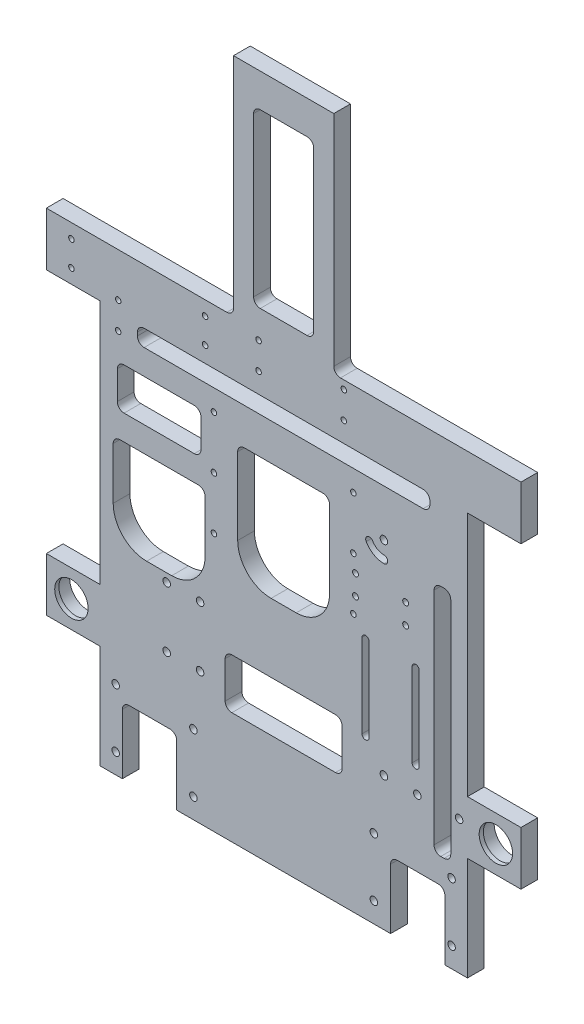
SolidWorks part; units mm, degrees
ref_plane "Front" through (0, 0, 0) normal (0, 0, 1) x (1, 0, 0)
ref_plane "Top" through (0, 0, 0) normal (0, 1, 0) x (1, 0, 0)
ref_plane "Right" through (0, 0, 0) normal (1, 0, 0) x (0, 0, -1)
sketch "Esquisse1" plane through (0, 0, 0) normal (0, 0, 1) x (1, 0, 0)
  line L1 (0, 0) -> (220, 0)
  line L2 (0, 0) -> (0, 285)
  line L3 (0, 285) -> (220, 285)
  line L4 (220, 0) -> (220, 285)
  dimension "D1" = 220
  dimension "D2" = 285
extrude "Boss.-Extru.1" add sketch "Esquisse1" along normal blind 10
sketch "Esquisse2" plane through (0, 0, 0) normal (0, -1, 0) x (1, 0, 0)
  line L0 (0, 5) -> (220, 5) construction
  line L1 (0, 10) -> (0, 0) construction
  line L2 (220, 10) -> (220, 0) construction
  line L3 (110, 5) -> (110, 28.0559) construction
  circle A0 centre (110, 5) radius 2
  circle A1 centre (213, 5) radius 2
  circle A2 centre (7, 5) radius 2
  dimension "D1" = 4
  dimension "D2" = 103
extrude "Enlèv. mat.-Extru.1" cut sketch "Esquisse2" against normal blind 8
sketch "Esquisse3" plane through (0, 0, 10) normal (0, 0, 1) x (1, 0, 0)
  line L0 (110, 0) -> (110, 285) construction
  line L1 (0, 0) -> (220, 0) construction
  line L2 (220, 285) -> (0, 285) construction
  line L3 (82.5, 208) -> (137.5, 208)
  line L4 (137.5, 208) -> (137.5, 138)
  line L5 (137.5, 138) -> (82.5, 138)
  line L6 (82.5, 208) -> (82.5, 138)
  line L8 (8, 175) -> (63, 175)
  line L9 (8, 175) -> (8, 120)
  line L10 (8, 120) -> (63, 120)
  line L11 (63, 175) -> (63, 120)
  line L12 (200, 55) -> (210, 55)
  line L13 (200, 55) -> (200, 195)
  line L14 (200, 195) -> (210, 195)
  line L15 (210, 55) -> (210, 195)
  point P11 (110, 138)
  point P12 (110, 208)
  dimension "D1" = 70
  dimension "D2" = 55
  dimension "D3" = 138
  dimension "D4" = 55
  dimension "D5" = 47
  dimension "D6" = 55
  dimension "D7" = 120
  dimension "D8" = 140
  dimension "D9" = 55
  dimension "D10" = 90
  dimension "D11" = 10
extrude "Enlèv. mat.-Extru.2" cut sketch "Esquisse3" against normal through all both and the other way through all
sketch "Esquisse5" plane through (0, 0, 10) normal (0, 0, 1) x (1, 0, 0)
  line L0 (110, 230) -> (110, 0) construction
  line L1 (22.5, 240) -> (197.5, 240)
  line L2 (22.5, 240) -> (22.5, 230)
  line L3 (22.5, 230) -> (197.5, 230)
  line L4 (197.5, 240) -> (197.5, 230)
  line L5 (0, 0) -> (220, 0) construction
  dimension "D1" = 175
  dimension "D2" = 10
  dimension "D3" = 230
extrude "Enlèv. mat.-Extru.3" cut sketch "Esquisse5" against normal through all both and the other way through all
sketch "Esquisse6" plane through (0, 0, 10) normal (0, 0, 1) x (1, 0, 0)
  line L0 (170, 80) -> (190, 80) construction
  line L1 (0, 0) -> (220, 0) construction
  line L2 (137.5, 138) -> (82.5, 138) construction
  line L3 (215, 80) -> (190, 80) construction
  line L4 (168, 193.9299) -> (168, 170.25) construction
  line L5 (186.4274, 170.25) -> (149.5726, 170.25) construction
  line L6 (0, 285) -> (0, 0) construction
  circle A0 centre (190, 80) radius 2.25
  circle A1 centre (170, 80) radius 2.25
  circle A2 centre (215, 80) radius 2.25
  circle A3 centre (153, 176.25) radius 1.75
  circle A4 centre (183, 176.25) radius 1.75
  circle A5 centre (183, 164.25) radius 1.75
  circle A6 centre (153, 164.25) radius 1.75
  point P8 (110, 138)
  dimension "D1" = 4.5
  dimension "D3" = 80
  dimension "D6" = 30
  dimension "D7" = 12
  dimension "D8" = 3.5
  dimension "D2" = 20
  dimension "D4" = 60
  dimension "D5" = 25
  dimension "D9" = 168
  dimension "D10" = 170.25
extrude "Enlèv. mat.-Extru.4" cut sketch "Esquisse6" against normal through all both and the other way through all
sketch "Esquisse7" plane through (0, 0, 10) normal (0, 0, 1) x (1, 0, 0)
  line L0 (110, 0) -> (110, 285) construction
  line L1 (0, 0) -> (220, 0) construction
  line L2 (220, 285) -> (0, 285) construction
  line L3 (68.285, 186) -> (68.285, 217.4) construction
  line L4 (68.285, 186) -> (110, 186) construction
  line L5 (151.715, 186) -> (151.715, 217.4) construction
  line L6 (95, 268) -> (120.5, 268) construction
  line L7 (120.5, 268) -> (120.5, 260) construction
  line L8 (120.5, 260) -> (137.9818, 260) construction
  line L9 (95, 252) -> (120.5, 252) construction
  line L10 (22.5, 240) -> (197.5, 240) construction
  circle A0 centre (68.285, 217.4) radius 1.65
  circle A1 centre (68.285, 186) radius 1.65
  circle A2 centre (68.285, 154.6) radius 1.65
  circle A3 centre (151.715, 154.6) radius 1.65
  circle A4 centre (151.715, 186) radius 1.65
  circle A5 centre (151.715, 217.4) radius 1.65
  circle A6 centre (95, 268) radius 1.65
  circle A7 centre (146, 268) radius 1.65
  circle A8 centre (146, 252) radius 1.65
  circle A9 centre (95, 252) radius 1.65
  dimension "D1" = 31.4
  dimension "D2" = 3.3
  dimension "D5" = 16
  dimension "D6" = 51
  dimension "D9" = 3.3
  dimension "D7" = 15
  dimension "D3" = 83.43
  dimension "D4" = 186
  dimension "D8" = 20
extrude "Enlèv. mat.-Extru.5" cut sketch "Esquisse7" against normal through all both and the other way through all
sketch "Esquisse8" plane through (0, 0, 10) normal (0, 0, 1) x (1, 0, 0)
  line L0 (110, 0) -> (110, 285) construction
  line L1 (0, 0) -> (220, 0) construction
  line L2 (220, 285) -> (0, 285) construction
  line L3 (174, 0) -> (174, 40)
  line L4 (13.5, 0) -> (46, 0)
  line L5 (13.5, 0) -> (13.5, 40)
  line L6 (13.5, 40) -> (46, 40)
  line L7 (46, 0) -> (46, 40)
  line L8 (206.5, 40) -> (174, 40)
  line L9 (206.5, 0) -> (206.5, 40)
  line L10 (206.5, 0) -> (174, 0)
  dimension "D1" = 128
  dimension "D2" = 32.5
  dimension "D3" = 40
extrude "Enlèv. mat.-Extru.6" cut sketch "Esquisse8" against normal through all both and the other way through all
fillet "Congé1" radius 20 4 edges at (137.5, 138, 5) (82.5, 138, 5) (63, 120, 5) (8, 120, 5)
sketch "Esquisse9" plane through (0, 0, 10) normal (0, 0, 1) x (1, 0, 0)
  line L0 (189, 145) -> (189, 95) construction
  line L1 (191.1, 145) -> (191.1, 95)
  line L2 (186.9, 145) -> (186.9, 95)
  line L3 (189, 120) -> (159, 120) construction
  line L4 (174, 120) -> (174, 121.5076) construction
  line L5 (159, 95) -> (159, 145) construction
  line L6 (156.9, 95) -> (156.9, 145)
  line L7 (161.1, 95) -> (161.1, 145)
  line L9 (210, 55) -> (200, 55) construction
  line L10 (200, 55) -> (200, 195) construction
  arc A0 (191.1, 145) -> (186.9, 145) centre (189, 145) ccw
  arc A1 (186.9, 95) -> (191.1, 95) centre (189, 95) ccw
  arc A2 (156.9, 95) -> (161.1, 95) centre (159, 95) ccw
  arc A3 (161.1, 145) -> (156.9, 145) centre (159, 145) ccw
  point P2 (189, 120)
  point P13 (159, 120)
  dimension "D1" = 4.2
  dimension "D2" = 30
  dimension "D3" = 11
  dimension "D4" = 40
  dimension "D5" = 50
extrude "Enlèv. mat.-Extru.7" cut sketch "Esquisse9" against normal through all both and the other way through all
sketch "Esquisse10" plane through (0, 0, 10) normal (0, 0, 1) x (1, 0, 0)
  line L0 (9.5, 0) -> (9.5, 52.9697) construction
  line L1 (0, 0) -> (13.5, 0) construction
  line L2 (0, 285) -> (0, 0) construction
  line L3 (110, 0) -> (110, 48.9194) construction
  line L4 (46, 0) -> (174, 0) construction
  line L5 (32.75, 0) -> (32.75, 52.9697) construction
  circle A0 centre (9.5, 12) radius 2.25
  circle A1 centre (9.5, 47) radius 2.25
  circle A2 centre (210.5, 47) radius 2.25
  circle A3 centre (210.5, 12) radius 2.25
  circle A4 centre (56, 47) radius 2.25
  circle A5 centre (56, 12) radius 2.25
  circle A6 centre (164, 12) radius 2.25
  circle A7 centre (164, 47) radius 2.25
  dimension "D2" = 4.5
  dimension "D3" = 35
  dimension "D4" = 12
  dimension "D5" = 46.5
  dimension "D1" = 9.5
extrude "Enlèv. mat.-Extru.8" cut sketch "Esquisse10" against normal through all both and the other way through all
sketch "Esquisse11" plane through (0, 0, 10) normal (0, 0, 1) x (1, 0, 0)
  line L0 (110, 67) -> (110, 0) construction
  line L1 (75, 97) -> (145, 97)
  line L2 (75, 97) -> (75, 67)
  line L3 (75, 67) -> (145, 67)
  line L4 (145, 97) -> (145, 67)
  line L5 (46, 0) -> (174, 0) construction
  dimension "D1" = 70
  dimension "D2" = 30
  dimension "D3" = 67
extrude "Enlèv. mat.-Extru.9" cut sketch "Esquisse11" against normal through all both and the other way through all
sketch "Esquisse12" plane through (0, 0, 10) normal (0, 0, 1) x (1, 0, 0)
  line L0 (220, 0) -> (220, 285) construction
  line L1 (46, 0) -> (174, 0) construction
  line L2 (170, 202) -> (161.3397, 197) construction
  line L3 (170, 192) -> (170, 202) construction
  circle A0 centre (170, 202) radius 2.25
  arc A1 (161.3397, 197) -> (170, 192) centre (170, 202) ccw construction
  arc A2 (159.3912, 195.875) -> (170, 189.75) centre (170, 202) ccw
  arc A3 (163.2883, 198.125) -> (170, 194.25) centre (170, 202) ccw
  arc A4 (163.2883, 198.125) -> (159.3912, 195.875) centre (161.3397, 197) ccw
  arc A5 (170, 189.75) -> (170, 194.25) centre (170, 192) ccw
  point P9 (165, 193.3397)
  dimension "D1" = 4.5
  dimension "D2" = 50
  dimension "D3" = 202
  dimension "D4" = 4.5
  dimension "D5" = 10
  dimension "D6" = 60
extrude "Enlèv. mat.-Extru.10" cut sketch "Esquisse12" against normal through all both and the other way through all
sketch "Esquisse13" plane through (0, 0, 10) normal (0, 0, 1) x (1, 0, 0)
  line L0 (50, 123.132) -> (50, 97) construction
  line L1 (50, 97) -> (30.3926, 97) construction
  line L2 (46, 0) -> (174, 0) construction
  line L3 (0, 285) -> (0, 0) construction
  circle A0 centre (40, 115) radius 2.25
  circle A1 centre (60, 115) radius 2.25
  circle A2 centre (60, 79) radius 2.25
  circle A3 centre (40, 79) radius 2.25
  dimension "D1" = 36
  dimension "D2" = 20
  dimension "D3" = 4.5
  dimension "D4" = 97
  dimension "D5" = 40
extrude "Enlèv. mat.-Extru.11" cut sketch "Esquisse13" against normal through all both and the other way through all
sketch "Esquisse14" plane through (0, 0, 10) normal (0, 0, 1) x (1, 0, 0)
  line L0 (110, 0) -> (110, 159.9943) construction
  line L1 (0, 285) -> (80, 285)
  line L2 (0, 285) -> (0, 273)
  line L3 (0, 273) -> (80, 273)
  line L4 (80, 285) -> (80, 273)
  line L5 (46, 0) -> (174, 0) construction
  line L6 (140, 285) -> (140, 273)
  line L7 (220, 273) -> (140, 273)
  line L8 (220, 285) -> (220, 273)
  line L9 (220, 285) -> (140, 285)
  dimension "D1" = 12
  dimension "D2" = 80
extrude "Enlèv. mat.-Extru.12" cut sketch "Esquisse14" against normal through all both and the other way through all
sketch "Esquisse15" plane through (0, 0, 10) normal (0, 0, 1) x (1, 0, 0)
  line L0 (140, 285) -> (80, 285) construction
  line L1 (80, 285) -> (140, 285)
  line L2 (80, 285) -> (80, 408)
  line L3 (80, 408) -> (140, 408)
  line L4 (140, 285) -> (140, 408)
  line L5 (110, 408) -> (110, 0) construction
  line L6 (46, 0) -> (174, 0) construction
  dimension "D1" = 60
  dimension "D2" = 123
extrude "Boss.-Extru.2" add sketch "Esquisse15" against normal up to vertex (10 mm away) up to point (13.5, 0, 0)
sketch "Esquisse16" plane through (0, 0, 10) normal (0, 0, 1) x (1, 0, 0)
  line L0 (110, 388) -> (110, 408) construction
  line L1 (92, 285) -> (128, 285)
  line L2 (92, 285) -> (92, 388)
  line L3 (92, 388) -> (128, 388)
  line L4 (128, 285) -> (128, 388)
  line L5 (140, 408) -> (80, 408) construction
  line L6 (140, 273) -> (140, 408) construction
  line L7 (80, 273) -> (0, 273) construction
  dimension "D1" = 12
  dimension "D2" = 20
  dimension "D3" = 12
extrude "Enlèv. mat.-Extru.13" cut sketch "Esquisse16" against normal through all both and the other way through all
sketch "Esquisse17" plane through (0, 0, 10) normal (0, 0, 1) x (1, 0, 0)
  line L0 (110, 0) -> (110, -39.2027) construction
  line L1 (220, 273) -> (252, 273)
  line L2 (220, 273) -> (220, 241)
  line L3 (220, 241) -> (252, 241)
  line L4 (252, 273) -> (252, 241)
  line L5 (46, 0) -> (174, 0) construction
  line L6 (-32, 273) -> (-32, 241)
  line L7 (0, 241) -> (-32, 241)
  line L8 (0, 273) -> (0, 241)
  line L9 (0, 273) -> (-32, 273)
  line L10 (0, 273) -> (0, 0) construction
  line L11 (0, 62) -> (-32, 62)
  line L12 (0, 62) -> (0, 94)
  line L13 (0, 94) -> (-32, 94)
  line L14 (-32, 62) -> (-32, 94)
  line L15 (252, 62) -> (252, 94)
  line L16 (220, 94) -> (252, 94)
  line L17 (220, 62) -> (220, 94)
  line L18 (220, 62) -> (252, 62)
  point P19 (0, 0)
  dimension "D1" = 32
  dimension "D2" = 32
  dimension "D3" = 32
  dimension "D4" = 62
extrude "Boss.-Extru.3" add sketch "Esquisse17" against normal up to vertex (10 mm away) up to point (140, 273, 0)
sketch "Esquisse18" plane through (0, 0, 10) normal (0, 0, 1) x (1, 0, 0)
  line L0 (35.5, 190) -> (35.5, 175) construction
  line L1 (10.5, 190) -> (60.5, 190)
  line L2 (10.5, 190) -> (10.5, 215)
  line L3 (10.5, 215) -> (60.5, 215)
  line L4 (60.5, 190) -> (60.5, 215)
  line L5 (8, 175) -> (63, 175) construction
  dimension "D1" = 25
  dimension "D2" = 50
  dimension "D3" = 15
extrude "Enlèv. mat.-Extru.14" cut sketch "Esquisse18" against normal through all both and the other way through all
fillet "Congé2" radius 4 30 edges at (137.5, 208, 5) (82.5, 208, 5) (197.5, 230, 5) (197.5, 240, 5) (22.5, 240, 5) (22.5, 230, 5) (63, 175, 5) (8, 175, 5) (200, 195, 5) (210, 195, 5) (210, 55, 5) (200, 55, 5) (206.5, 40, 5) (174, 40, 5) (46, 40, 5) (13.5, 40, 5) (75, 67, 5) (145, 67, 5) (145, 97, 5) (75, 97, 5) (92, 388, 5) (128, 388, 5) (128, 285, 5) (92, 285, 5) (140, 273, 5) (80, 273, 5) (10.5, 215, 5) (60.5, 215, 5) (60.5, 190, 5) (10.5, 190, 5)
sketch "Esquisse19" plane through (0, 0, 10) normal (0, 0, 1) x (1, 0, 0)
  line L0 (-32, 257) -> (54.3473, 257) construction
  line L1 (-32, 273) -> (-32, 241) construction
  line L2 (23, 257) -> (23, 269.1) construction
  line L3 (11, 230.8) -> (11, 246.8) construction
  circle A0 centre (-17, 264.5) radius 1.65
  circle A1 centre (-17, 249.5) radius 1.65
  circle A2 centre (63, 249.5) radius 1.65
  circle A3 centre (63, 264.5) radius 1.65
  circle A4 centre (11, 246.8) radius 1.65
  circle A5 centre (11, 230.8) radius 1.65
  dimension "D2" = 80
  dimension "D3" = 3.3
  dimension "D5" = 28
  dimension "D6" = 16
  dimension "D7" = 10.2
  dimension "D1" = 15
  dimension "D4" = 55
extrude "Enlèv. mat.-Extru.15" cut sketch "Esquisse19" against normal through all both and the other way through all
sketch "Esquisse20" plane through (0, 0, 0) normal (0, 0, 1) x (1, 0, 0)
  line L0 (-32, 78) -> (-17, 78) construction
  line L1 (-32, 94) -> (-32, 62) construction
  line L2 (110, 0) -> (110, 74.504) construction
  line L3 (46, 0) -> (174, 0) construction
  line L4 (252, 78) -> (237, 78) construction
  circle A0 centre (-17, 78) radius 11.025
  circle A1 centre (237, 78) radius 11.025
  dimension "D1" = 22.05
  dimension "D2" = 15
extrude "Enlèv. mat.-Extru.16" cut sketch "Esquisse20" along normal blind 7.5
sketch "Esquisse21" plane through (0, 0, 7.5) normal (0, 0, -1) x (-1, 0, 0)
  line L0 (-110, 0) -> (-110, 78) construction
  line L1 (-46, 0) -> (-174, 0) construction
  circle A0 centre (17, 78) radius 10
  circle A1 centre (-237, 78) radius 10
  dimension "D1" = 20
extrude "Enlèv. mat.-Extru.17" cut sketch "Esquisse21" against normal through all both and the other way through all
